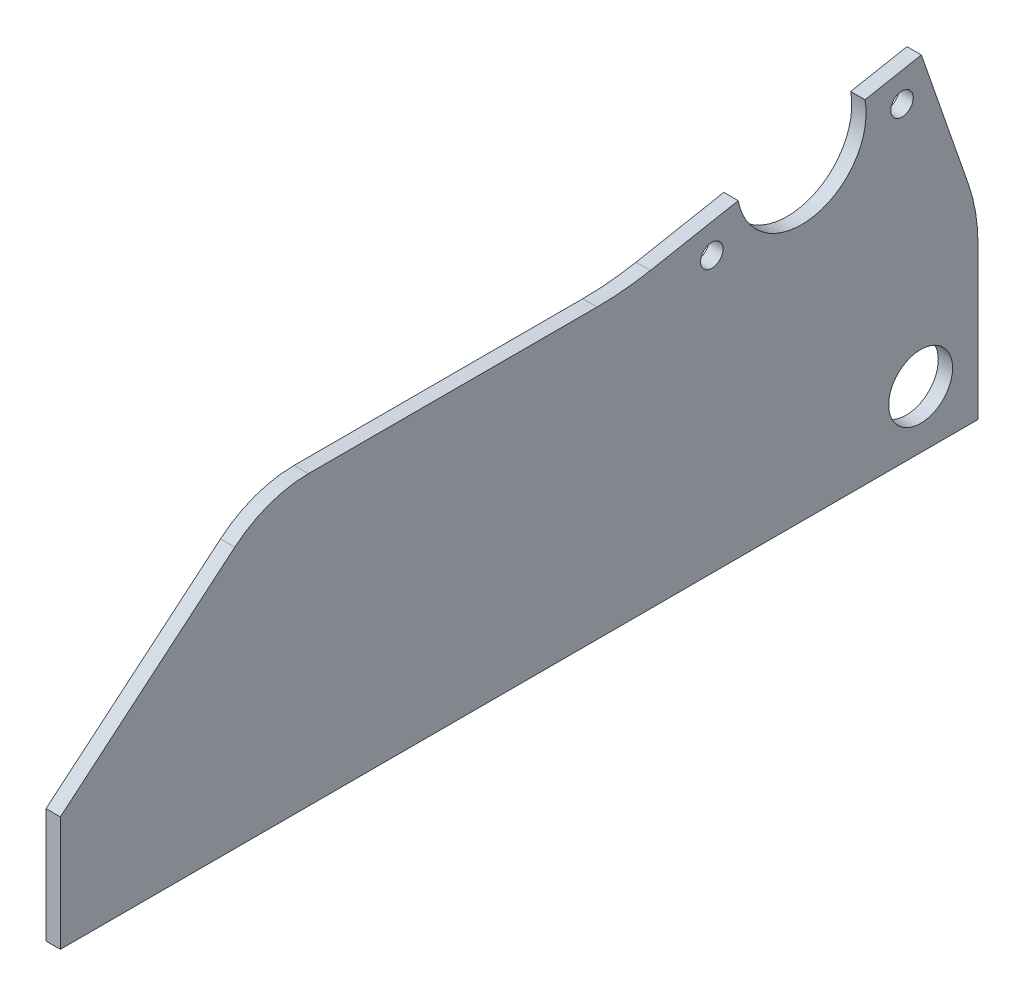
SolidWorks part; units mm, degrees
material "6061-T6 (SS)"
ref_plane "Front Plane" through (0, 0, 0) normal (0, 0, 1) x (1, 0, 0)
ref_plane "Top Plane" through (0, 0, 0) normal (0, 1, 0) x (1, 0, 0)
ref_plane "Right Plane" through (0, 0, 0) normal (1, 0, 0) x (0, 0, -1)
sketch "Sketch1" plane through (0, 0, 0) normal (1, 0, 0) x (0, 0, -1)
  line L0 (0, -38.1) -> (0, 1.9909)
  line L7 (-12.543, 38.1) -> (-25.0221, 35.7419)
  line L8 (-53.1002, 30.4361) -> (-78.3936, 25.6566)
  line L10 (-78.3936, 25.6566) -> (-148.2436, 25.6566)
  line L13 (-203.2, -38.1) -> (0, -38.1)
  line L14 (-203.2, -38.1) -> (-203.2, -12.7)
  line L15 (-203.2, -12.7) -> (-164.5704, 19.7141)
  line L16 (-203.2, -12.7) -> (0, -12.7) construction
  line L17 (-12.543, 38.1) -> (0, 1.9909)
  arc A2 (-25.0221, 35.7419) -> (-53.1002, 30.4361) centre (-39.0612, 33.089) cw
  arc A4 (-148.2436, 25.6566) -> (-164.5704, 19.7141) centre (-148.2436, 0.2566) ccw
  point P4 (0, 0)
  dimension "D1" = 28.575
  dimension "D4" = 25.4
  dimension "D7" = 25.4
  dimension "D2" = 76.2
  dimension "D6" = 203.2
  dimension "D8" = 50
  dimension "D9" = 69.85
extrude "Boss-Extrude1" add sketch "Sketch1" along normal blind 3.175
hole_wizard "#10 Clearance Hole1" positions "Sketch2" profile "Sketch3" hole size "#10" standard "ANSI Inch" end condition through all
sketch "Sketch2" plane through (3.175, 0, 0) normal (1, 0, 0) x (0, 0, -1)
  line L0 (-53.1002, 30.4361) -> (-78.3936, 25.6566) construction
  line L1 (-58.9407, 22.8701) -> (-16.8235, 30.8287) construction
  line L3 (-37.8821, 26.8494) -> (-39.0612, 33.089) construction
  line L4 (-12.543, 38.1) -> (-25.0221, 35.7419) construction
  point P0 (-58.9407, 22.8701)
  point P2 (-16.8235, 30.8287)
  dimension "D1" = 42.8625
  dimension "D2" = 6.35
sketch "Sketch3" plane through (3.175, 22.8701, 58.9407) normal (0, 1, 0) x (0, 0, -1)
  line L0 (0, 0) -> (0, 3.175)
  line L1 (0, 3.175) -> (2.4892, 3.175)
  line L2 (2.4892, 3.175) -> (2.4892, 0)
  line L5 (2.4892, 0) -> (0, 0)
  line L11 (0, -6.35) -> (0, 107.95) construction
  dimension "Thru Hole Dia." = 4.9784
  dimension "Thru Hole Depth" = 3.175
sketch "Sketch9" plane through (3.175, 0, 0) normal (1, 0, 0) x (0, 0, -1)
  line L2 (0, -38.1) -> (0, 1.9909) construction
  line L3 (-203.2, -38.1) -> (0, -38.1) construction
  circle A0 centre (-12.7, -25.4) radius 7.0739
  dimension "D1" = 14.1478
  dimension "D3" = 12.7
  dimension "D2" = 12.7
extrude "Cut-Extrude1" cut sketch "Sketch9" against normal through all
fillet "Fillet1" radius 38.1 1 edges at (1.5875, 1.9909, 0)
fillet "Fillet2" radius 63.5 1 edges at (1.5875, 25.6566, 78.3936)
